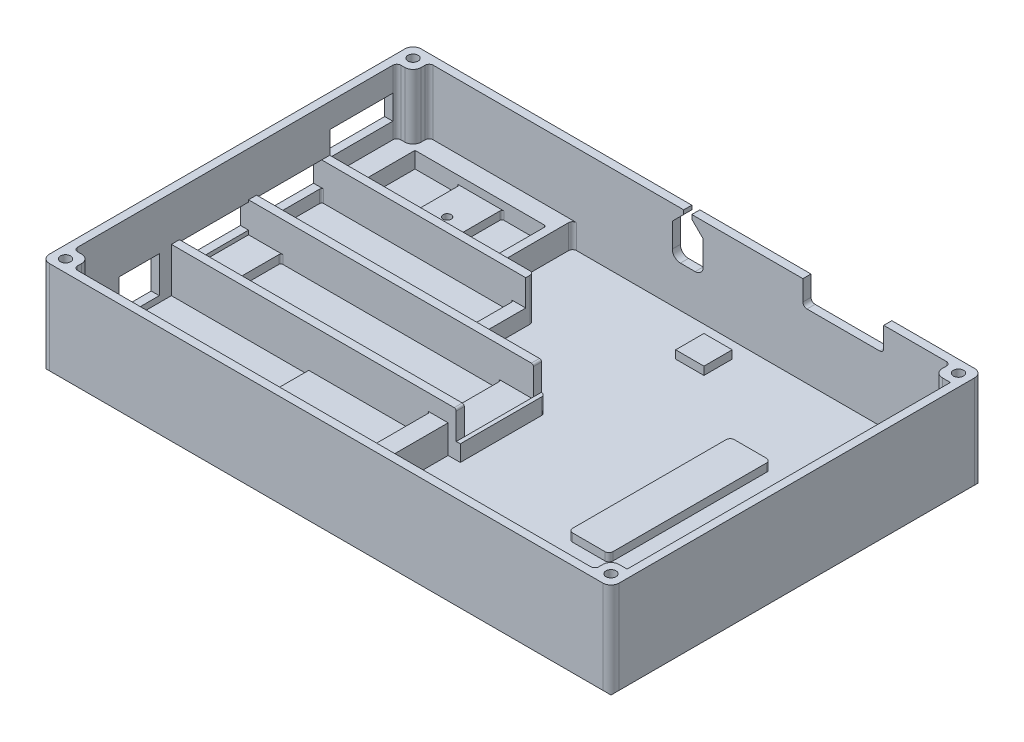
SolidWorks part; units mm, degrees
ref_plane "Front Plane" through (0, 0, 0) normal (0, 0, 1) x (1, 0, 0)
ref_plane "Top Plane" through (0, 0, 0) normal (0, 1, 0) x (1, 0, 0)
ref_plane "Right Plane" through (0, 0, 0) normal (1, 0, 0) x (0, 0, -1)
sketch "Sketch1" plane through (0, 0, 0) normal (0, 1, 0) x (1, 0, 0)
  line L1 (0, 0) -> (141, 0)
  line L2 (0, 0) -> (0, 92)
  line L3 (0, 92) -> (141, 92)
  line L4 (141, 0) -> (141, 92)
extrude "Base" add sketch "Sketch1" along normal blind 24
shell "Base Shell" thickness 2 removed face at (70.5, 24, -46)
chamfer "Chamfer1" distance 1 angle 45 4 edges at (0, 0, -46) (70.5, 0, -92) (141, 0, -46) (70.5, 0, 0)
sketch "Sketch2" plane through (0, 2, 0) normal (0, 1, 0) x (1, 0, 0)
  line L1 (0, 92) -> (6, 92)
  line L2 (0, 92) -> (0, 86)
  line L3 (0, 86) -> (6, 86)
  line L4 (6, 92) -> (6, 86)
  line L7 (141, 6) -> (135, 6)
  line L8 (0, 0) -> (6, 0)
  line L9 (0, 0) -> (0, 6)
  line L10 (0, 6) -> (6, 6)
  line L11 (6, 0) -> (6, 6)
  line L12 (135, 0) -> (135, 6)
  line L13 (141, 0) -> (135, 0)
  line L14 (141, 0) -> (141, 6)
  line L15 (141, 86) -> (135, 86)
  line L16 (135, 92) -> (135, 86)
  line L17 (141, 92) -> (135, 92)
  line L18 (141, 92) -> (141, 86)
extrude "Screw Support" add sketch "Sketch2" along normal blind 22
fillet "Base Corner Fillet" radius 2 4 edges at (141, 12.5, 0) (0, 12.5, 0) (0, 12.5, -92) (141, 12.5, -92)
fillet "Inner screw fillet" radius 2 4 edges at (135, 13, -86) (6, 13, -86) (6, 13, -6) (135, 13, -6)
sketch "Sketch5" plane through (0, 24, 0) normal (0, 1, 0) x (1, 0, 0)
  circle A0 centre (3, 89) radius 1.26
  circle A1 centre (3, 3) radius 1.26
  circle A2 centre (138, 3) radius 1.26
  circle A3 centre (138, 89) radius 1.26
extrude "Screw hole cut" cut sketch "Sketch5" against normal blind 15
sketch "Sketch7" plane through (0, 2, 0) normal (0, 1, 0) x (1, 0, 0)
  line L1 (2, 90) -> (41.5, 90)
  line L2 (2, 90) -> (2, 67.4)
  line L3 (2, 67.4) -> (41.5, 67.4)
  line L4 (41.5, 90) -> (41.5, 67.4)
extrude "Temp base extrude" add sketch "Sketch7" along normal blind 6
sketch "Sketch8" plane through (0, 8, 0) normal (0, 1, 0) x (1, 0, 0)
  line L15 (7, 85.5) -> (39.5, 85.5)
  line L16 (7, 85.5) -> (7, 69.4)
  line L17 (7, 69.4) -> (39.5, 69.4)
  line L18 (39.5, 85.5) -> (39.5, 69.4)
extrude "Temp base cut" cut sketch "Sketch8" against normal blind 2
sketch "Sketch9" plane through (0, 6, 0) normal (0, 1, 0) x (1, 0, 0)
  line L10 (7, 69.4) -> (39.5, 69.4) construction
  line L11 (7, 85.5) -> (18, 85.5)
  line L12 (7, 85.5) -> (7, 69.4)
  line L13 (7, 69.4) -> (18, 69.4)
  line L14 (18, 85.5) -> (18, 69.4)
  line L16 (39.5, 85.5) -> (28.5, 85.5)
  line L17 (39.5, 85.5) -> (39.5, 69.4)
  line L18 (39.5, 69.4) -> (28.5, 69.4)
  line L19 (28.5, 85.5) -> (28.5, 69.4)
extrude "Temp pins cut" cut sketch "Sketch9" against normal blind 2
sketch "Sketch10" plane through (0, 6, 0) normal (0, 1, 0) x (1, 0, 0)
  circle A0 centre (23.25, 77.2) radius 1
extrude "Temp screw hole cut" cut sketch "Sketch10" against normal blind 3
sketch "Sketch11" plane through (2, 0, 0) normal (1, 0, 0) x (0, 0, -1)
  line L4 (69.4, 12) -> (85, 12)
  line L5 (69.4, 12) -> (69.4, 18)
  line L6 (69.4, 18) -> (85, 18)
  line L7 (85, 12) -> (85, 18)
extrude "Temp output cut" cut sketch "Sketch11" against normal blind 3
sketch "Sketch13" plane through (0, 2, 0) normal (0, 1, 0) x (1, 0, 0)
  line L1 (2, 69.4) -> (52.5, 69.4)
  line L2 (2, 69.4) -> (2, 51.3)
  line L3 (2, 51.3) -> (52.5, 51.3)
  line L4 (52.5, 69.4) -> (52.5, 51.3)
extrude "Dimmer Base" add sketch "Sketch13" along normal blind 10.5
sketch "Sketch14" plane through (0, 12.5, 0) normal (0, 1, 0) x (1, 0, 0)
  line L0 (52.5, 51.3) -> (52.5, 69.4) construction
  line L1 (2, 51.3) -> (52.5, 51.3)
  line L2 (2, 51.3) -> (2, 67.4)
  line L3 (2, 67.4) -> (52.5, 67.4)
  line L4 (52.5, 51.3) -> (52.5, 67.4)
extrude "Dimmer Base Cut" cut sketch "Sketch14" against normal blind 9.1
sketch "Sketch16" plane through (0, 2, 0) normal (0, 1, 0) x (1, 0, 0)
  line L1 (52.5, 69.4) -> (49.5, 69.4)
  line L2 (52.5, 69.4) -> (52.5, 51.3)
  line L3 (52.5, 51.3) -> (49.5, 51.3)
  line L4 (49.5, 69.4) -> (49.5, 51.3)
extrude "Boss-Extrude5" add sketch "Sketch16" along normal blind 4
sketch "Sketch17" plane through (2, 0, 0) normal (1, 0, 0) x (0, 0, -1)
  line L1 (67.4, 3.4) -> (67.4, 12.5) construction
  line L2 (51.3, 6.5) -> (67.4, 6.5)
  line L3 (51.3, 6.5) -> (51.3, 12.5)
  line L4 (51.3, 12.5) -> (67.4, 12.5)
  line L5 (67.4, 6.5) -> (67.4, 12.5)
extrude "Cut-Extrude9" cut sketch "Sketch17" against normal blind 5
sketch "Sketch19" plane through (0, 2, 0) normal (0, 1, 0) x (1, 0, 0)
  line L1 (2, 51.3) -> (72.5, 51.3)
  line L2 (2, 51.3) -> (2, 30.2)
  line L3 (2, 30.2) -> (72.5, 30.2)
  line L4 (72.5, 51.3) -> (72.5, 30.2)
extrude "Relay Base" add sketch "Sketch19" along normal blind 11
sketch "Sketch20" plane through (0, 13, 0) normal (0, 1, 0) x (1, 0, 0)
  line L4 (2, 86) -> (2, 6) construction
  line L11 (2, 49.3) -> (72.5, 49.3)
  line L12 (2, 49.3) -> (2, 32.2)
  line L13 (2, 32.2) -> (72.5, 32.2)
  line L14 (72.5, 49.3) -> (72.5, 32.2)
  line L15 (72.5, 30.2) -> (72.5, 51.3) construction
extrude "Relay Base Cut" cut sketch "Sketch20" against normal blind 7.5
sketch "Sketch24" plane through (0, 5.5, 0) normal (0, 1, 0) x (1, 0, 0)
  line L1 (72.5, 49.3) -> (2, 49.3) construction
  line L3 (2, 32.2) -> (72.5, 32.2) construction
  line L4 (10, 49.3) -> (64.5, 49.3)
  line L5 (10, 49.3) -> (10, 32.2)
  line L6 (10, 32.2) -> (64.5, 32.2)
  line L7 (64.5, 49.3) -> (64.5, 32.2)
extrude "Relay Pins Cut" cut sketch "Sketch24" against normal blind 2.1
sketch "Sketch23" plane through (0, 2, 0) normal (0, 1, 0) x (1, 0, 0)
  line L1 (72.5, 51.3) -> (73.5, 51.3)
  line L2 (72.5, 51.3) -> (72.5, 30.2)
  line L3 (72.5, 30.2) -> (73.5, 30.2)
  line L4 (73.5, 51.3) -> (73.5, 30.2)
extrude "Relay Support Cut" add sketch "Sketch23" along normal blind 4
sketch "Sketch30" plane through (2, 0, 0) normal (1, 0, 0) x (0, 0, -1)
  line L0 (49.3, 5.5) -> (49.3, 13) construction
  line L1 (49.3, 6.5) -> (32.2, 6.5)
  line L2 (49.3, 6.5) -> (49.3, 12.5)
  line L3 (49.3, 12.5) -> (32.2, 12.5)
  line L4 (32.2, 6.5) -> (32.2, 12.5)
  line L5 (32.2, 5.5) -> (32.2, 13) construction
extrude "Relay Output Cut" cut sketch "Sketch30" against normal blind 16
sketch "Sketch22" plane through (0, 2, 0) normal (0, 1, 0) x (1, 0, 0)
  line L0 (78, 86) -> (85, 86)
  line L5 (85, 86) -> (85, 79)
  line L6 (85, 79) -> (78, 79)
  line L9 (78, 86) -> (78, 79)
  line L10 (78, 8) -> (85, 8)
  line L11 (85, 8) -> (85, 15)
  line L12 (85, 15) -> (78, 15)
  line L13 (78, 8) -> (78, 15)
  line L14 (139, 8) -> (139, 15)
  line L15 (132, 15) -> (139, 15)
  line L16 (132, 8) -> (132, 15)
  line L17 (139, 8) -> (132, 8)
  line L18 (139, 86) -> (132, 86)
  line L19 (132, 86) -> (132, 79)
  line L20 (132, 79) -> (139, 79)
  line L21 (139, 86) -> (139, 79)
extrude "Boss-Extrude13" add sketch "Sketch22" along normal blind 2
sketch "Sketch32" plane through (0, 2, 0) normal (0, 1, 0) x (1, 0, 0)
  line L3 (103.5, 27) -> (103.5, 67)
  line L6 (103.5, 67) -> (113.5, 67)
  line L7 (113.5, 27) -> (113.5, 67)
  line L11 (103.5, 27) -> (113.5, 27)
extrude "Support for esp32" add sketch "Sketch32" along normal blind 2
sketch "Sketch34" plane through (0, 2, 0) normal (0, 1, 0) x (1, 0, 0)
  line L1 (70.5, 30.2) -> (36, 30.2)
  line L3 (70.5, 30.2) -> (70.5, 13.2)
  line L12 (70.5, 13.2) -> (36, 13.2)
  line L13 (36, 30.2) -> (36, 13.2)
extrude "PSU part base" add sketch "Sketch34" along normal blind 7
sketch "Sketch35" plane through (0, 9, 0) normal (0, 1, 0) x (1, 0, 0)
  line L6 (36, 30.2) -> (66, 30.2)
  line L7 (36, 30.2) -> (36, 15.2)
  line L8 (36, 15.2) -> (66, 15.2)
  line L9 (66, 30.2) -> (66, 15.2)
extrude "PSU part cut" cut sketch "Sketch35" against normal blind 6
sketch "Sketch40" plane through (0, 0, 0) normal (-1, 0, 0) x (0, 0, 1)
  line L3 (-27.2, 12.5) -> (-17.2, 12.5)
  line L4 (-27.2, 12.5) -> (-27.2, 3.5)
  line L5 (-27.2, 3.5) -> (-17.2, 3.5)
  line L6 (-17.2, 12.5) -> (-17.2, 3.5)
extrude "PSU Cut" cut sketch "Sketch40" against normal blind 10
sketch "Sketch41" plane through (0, 0, -2) normal (0, 0, -1) x (-1, 0, 0)
  line L1 (-53, 1) -> (-27.5, 1)
  line L2 (-41, 17.5) -> (-27.5, 17.5)
  line L6 (-2, 1) -> (-139, 1) construction
  line L7 (-41, 17.5) -> (-53, 17.5)
  line L10 (-53, 17.5) -> (-53, 1)
  line L11 (-139, 1) -> (-2, 1) construction
  line L12 (-27.5, 1) -> (-27.5, 17.5)
extrude "Boss-Extrude14" add sketch "Sketch41" along normal blind 4
sketch "Sketch42" plane through (0, 17.5, 0) normal (0, 1, 0) x (1, 0, 0)
  line L1 (27.5, 6) -> (53, 6) construction
  line L3 (53, 6) -> (27.5, 6) construction
  line L4 (27.5, 2) -> (53, 2) construction
  line L5 (29.5, 6) -> (51, 6)
  line L6 (29.5, 6) -> (29.5, 2)
  line L7 (29.5, 2) -> (51, 2)
  line L8 (51, 6) -> (51, 2)
extrude "Cut-Extrude20" cut sketch "Sketch42" against normal blind 15.5
sketch "Sketch43" plane through (0, 2, 0) normal (0, 1, 0) x (1, 0, 0)
  line L0 (38.7896, 9.8552) -> (48.7896, 9.8552)
  line L1 (38.7896, 9.8552) -> (38.7896, 7.8552)
  line L9 (48.7896, 9.8552) -> (48.7896, 7.8552)
  line L10 (48.7896, 7.8552) -> (38.7896, 7.8552)
extrude "Boss-Extrude18" add sketch "Sketch43" along normal blind 10 contours L0 L9 L10 L1
fillet "0.5 mm fillet" radius 0.5 20 edges at (36, 9, -14.2) (72.5, 13, -50.3) (72.5, 13, -31.2) (66, 6, -15.2) (66, 6, -30.2) (64.5, 4.45, -32.2) (64.5, 4.45, -49.3) (10, 4.45, -32.2) (10, 4.45, -49.3) (49.5, 4.7, -51.3) (49.5, 4.7, -67.4) (2, 4.95, -51.3) (2, 4.95, -67.4) (18, 5, -69.4) (18, 5, -85.5) (28.5, 5, -85.5) (28.5, 5, -69.4) (39.5, 6, -69.4) (39.5, 6, -85.5) (7, 6, -69.4)
sketch "Sketch49" plane through (0, 0, -92) normal (0, 0, -1) x (-1, 0, 0)
  line L1 (-139, 24) -> (-2, 24) construction
  line L3 (-69, 24) -> (-71, 24)
  line L4 (-71, 24) -> (-71, 23)
  line L5 (-71, 23) -> (-73.8284, 20.1716)
  line L6 (-73.8284, 20.1716) -> (-73.8284, 12.1716)
  line L7 (-73.8284, 12.1716) -> (-66.1716, 12.1716)
  line L8 (-66.1716, 20.1716) -> (-66.1716, 12.1716)
  line L9 (-69, 23) -> (-66.1716, 20.1716)
  line L10 (-69, 24) -> (-69, 23)
  point P12 (-70, 12.1716)
extrude "Cut-Extrude23" cut sketch "Sketch49" against normal blind 10
fillet "Fillet3" radius 2 2 edges at (73.8284, 12.1716, -91) (66.1716, 12.1716, -91)
sketch "Sketch50" plane through (0, 24, 0) normal (0, 1, 0) x (1, 0, 0)
  line L1 (98.5, 90) -> (118.5, 90)
  line L2 (98.5, 90) -> (98.5, 92)
  line L3 (98.5, 92) -> (118.5, 92)
  line L4 (118.5, 90) -> (118.5, 92)
extrude "Cut-Extrude24" cut sketch "Sketch50" against normal blind 6 contours L3 L4 L1 L2
fillet "1 mm fillet" radius 1 18 edges at (41.5, 5, -90) (41.5, 5, -69.4) (52.5, 4, -51.3) (70.5, 5.5, -13.2) (73.5, 4, -51.3) (52.5, 7.25, -69.4) (103.5, 3, -67) (113.5, 3, -67) (103.5, 3, -27) (113.5, 3, -27) (135, 13, -2) (2, 13, -6) (6, 13, -2) (2, 16, -86) (6, 16, -90) (118.5, 18, -91) (98.5, 18, -91) (135, 13, -90)
sketch "Sketch51" plane through (0, 0, -92) normal (0, 0, -1) x (-1, 0, 0)
  line L0 (-6.5128, 16.5) -> (-5.8124, 16.5)
  line L1 (-5.5551, 14.6154) -> (-4.2692, 13)
  line L2 (-4.2692, 13) -> (-4.6577, 13)
  line L3 (-4.6577, 13) -> (-5.9435, 14.6154)
  line L4 (-5.9435, 14.6154) -> (-6.1987, 14.6154)
  line L5 (-6.1987, 14.6154) -> (-6.1987, 13)
  line L6 (-6.1987, 13) -> (-6.5128, 13)
  line L7 (-6.5128, 13) -> (-6.5128, 16.5)
  line L8 (-6.1987, 16.141) -> (-6.1987, 14.9744)
  line L9 (-6.1987, 14.9744) -> (-5.5579, 14.9695)
  line L10 (-5.5425, 16.141) -> (-6.1987, 16.141)
  line L11 (-13.109, 16.141) -> (-13.109, 16.5)
  line L12 (-13.109, 16.5) -> (-11.2692, 16.5)
  line L13 (-11.2692, 16.5) -> (-11.2692, 16.141)
  line L14 (-11.2692, 16.141) -> (-12.0321, 16.141)
  line L15 (-12.0321, 16.141) -> (-12.0321, 13)
  line L16 (-12.0321, 13) -> (-12.3462, 13)
  line L17 (-12.3462, 13) -> (-12.3462, 16.141)
  line L18 (-12.3462, 16.141) -> (-13.109, 16.141)
  line L19 (-14.9487, 16.5) -> (-13.3333, 13)
  line L20 (-13.3333, 13) -> (-13.6748, 13)
  line L21 (-13.6748, 13) -> (-14.1922, 14.1218)
  line L22 (-14.1922, 14.1218) -> (-15.7788, 14.1218)
  line L23 (-15.7788, 14.1218) -> (-16.3103, 13)
  line L24 (-16.3103, 13) -> (-16.6538, 13)
  line L25 (-16.6538, 13) -> (-14.9936, 16.5)
  line L26 (-14.9936, 16.5) -> (-14.9487, 16.5)
  line L27 (-14.9747, 15.8171) -> (-15.6078, 14.4808)
  line L28 (-15.6078, 14.4808) -> (-14.3577, 14.4808)
  line L29 (-14.3577, 14.4808) -> (-14.9747, 15.8171)
  line L30 (-19.9744, 13) -> (-19.9744, 16.5)
  line L31 (-19.9744, 16.5) -> (-19.9085, 16.5)
  line L32 (-19.9085, 16.5) -> (-17.5962, 13.7453)
  line L33 (-17.5962, 13.7453) -> (-17.5962, 16.5)
  line L34 (-17.5962, 16.5) -> (-17.2821, 16.5)
  line L35 (-17.2821, 16.5) -> (-17.2821, 13)
  line L36 (-17.2821, 13) -> (-17.3536, 13)
  line L37 (-17.3536, 13) -> (-19.6603, 15.7484)
  line L38 (-19.6603, 15.7484) -> (-19.6603, 13)
  line L39 (-19.6603, 13) -> (-19.9744, 13)
  line L40 (-21.1859, 16.5) -> (-20.8718, 16.5)
  line L41 (-20.8718, 16.5) -> (-20.8718, 13)
  line L42 (-20.8718, 13) -> (-21.1859, 13)
  line L43 (-21.1859, 13) -> (-21.1859, 16.5)
  line L44 (-22.1282, 15.9026) -> (-22.3974, 15.6474)
  line L45 (-22.2179, 14.3462) -> (-23.3846, 14.3462)
  line L46 (-23.3846, 14.3462) -> (-23.3846, 14.7051)
  line L47 (-23.3846, 14.7051) -> (-21.9038, 14.7051)
  line L48 (-26.3462, 15.9026) -> (-26.6154, 15.6474)
  line L49 (-26.4359, 14.3462) -> (-27.6026, 14.3462)
  line L50 (-27.6026, 14.3462) -> (-27.6026, 14.7051)
  line L51 (-27.6026, 14.7051) -> (-26.1218, 14.7051)
  line L52 (-31.8654, 16.5) -> (-30.25, 13)
  line L53 (-30.25, 13) -> (-30.5914, 13)
  line L54 (-30.5914, 13) -> (-31.1089, 14.1218)
  line L55 (-31.1089, 14.1218) -> (-32.6955, 14.1218)
  line L56 (-32.6955, 14.1218) -> (-33.227, 13)
  line L57 (-33.227, 13) -> (-33.5705, 13)
  line L58 (-33.5705, 13) -> (-31.9103, 16.5)
  line L59 (-31.9103, 16.5) -> (-31.8654, 16.5)
  line L60 (-31.8913, 15.8171) -> (-32.5244, 14.4808)
  line L61 (-32.5244, 14.4808) -> (-31.2743, 14.4808)
  line L62 (-31.2743, 14.4808) -> (-31.8913, 15.8171)
  line L63 (-34.2436, 15.9026) -> (-34.5128, 15.6474)
  line L64 (-34.3333, 14.3462) -> (-35.5, 14.3462)
  line L65 (-35.5, 14.3462) -> (-35.5, 14.7051)
  line L66 (-35.5, 14.7051) -> (-34.0192, 14.7051)
  spline S0 degree 3 poles (-5.8124, 16.5) (-5.7227, 16.4995) (-5.594, 16.4998) (-5.4305, 16.4931) (-5.3255, 16.489) (-5.2323, 16.4815) (-5.1311, 16.4727) (-5.0615, 16.4617) (-5.0194, 16.4523) knots 0 0 0 0 0.338434 0.484822 0.617158 0.734698 0.837385 1 1 1 1
  spline S1 degree 3 poles (-5.0194, 16.4523) (-4.9685, 16.4411) (-4.8943, 16.4178) (-4.8007, 16.3764) (-4.7349, 16.3404) (-4.6732, 16.2989) (-4.6148, 16.2524) (-4.5597, 16.2013) (-4.5099, 16.1443) (-4.463, 16.0844) (-4.4234, 16.0197) (-4.3892, 15.952) (-4.3621, 15.8807) (-4.3402, 15.8065) (-4.3192, 15.701) (-4.314, 15.6193) (-4.3141, 15.564) knots 0 0 0 0 0.127064 0.188745 0.249132 0.309453 0.369827 0.43065 0.492352 0.554072 0.61569 0.676798 0.738439 0.801317 0.865185 1 1 1 1
  spline S2 degree 3 poles (-4.3141, 15.564) (-4.3138, 15.4732) (-4.3293, 15.3384) (-4.389, 15.1711) (-4.4493, 15.057) (-4.5261, 14.954) (-4.6184, 14.8637) (-4.7263, 14.788) (-4.8267, 14.7356) (-4.9154, 14.702) (-4.9885, 14.6783) (-5.0681, 14.6601) (-5.1537, 14.6437) (-5.2454, 14.6314) (-5.3798, 14.6189) (-5.4838, 14.6156) (-5.5551, 14.6154) knots 0 0 0 0 0.153721 0.226714 0.299191 0.37119 0.443006 0.516689 0.593217 0.633873 0.676989 0.7229 0.771959 0.824211 0.879379 1 1 1 1
  spline S3 degree 3 poles (-5.5579, 14.9695) (-5.4999, 14.9685) (-5.4159, 14.9716) (-5.308, 14.978) (-5.2359, 14.9849) (-5.1699, 14.9939) (-5.11, 15.0051) (-5.0561, 15.0181) (-4.9932, 15.0383) (-4.9229, 15.0703) (-4.8466, 15.1169) (-4.7816, 15.1755) (-4.7267, 15.2424) (-4.6826, 15.3161) (-4.6407, 15.4224) (-4.628, 15.5075) (-4.6282, 15.5647) knots 0 0 0 0 0.138913 0.201185 0.259124 0.312255 0.360682 0.405086 0.445102 0.518778 0.589462 0.658462 0.727283 0.796322 0.863175 1 1 1 1
  spline S4 degree 3 poles (-4.6282, 15.5647) (-4.6284, 15.6203) (-4.64, 15.7043) (-4.6842, 15.8074) (-4.7284, 15.8795) (-4.7825, 15.945) (-4.8458, 16.0011) (-4.9167, 16.0473) (-4.9829, 16.0769) (-5.0422, 16.095) (-5.0936, 16.1077) (-5.1517, 16.118) (-5.2168, 16.1262) (-5.2886, 16.1332) (-5.3979, 16.1399) (-5.4833, 16.1412) (-5.5425, 16.141) knots 0 0 0 0 0.136365 0.204019 0.273064 0.342913 0.410965 0.479169 0.549308 0.587652 0.630647 0.678879 0.731934 0.791111 0.855283 1 1 1 1
  spline S5 degree 3 poles (-9.0929, 16.5897) (-8.9658, 16.589) (-8.7769, 16.5755) (-8.5352, 16.5175) (-8.3636, 16.4607) (-8.2011, 16.3848) (-8.0465, 16.2931) (-7.9001, 16.1846) (-7.7638, 16.0602) (-7.6392, 15.9248) (-7.5294, 15.7803) (-7.4373, 15.6276) (-7.3617, 15.4672) (-7.3025, 15.2993) (-7.2469, 15.0613) (-7.2305, 14.8764) (-7.2308, 14.7514) knots 0 0 0 0 0.130749 0.193413 0.254989 0.316114 0.377262 0.439401 0.502971 0.566525 0.628231 0.689091 0.749345 0.81017 0.87161 1 1 1 1
  spline S6 degree 3 poles (-7.2308, 14.7514) (-7.2305, 14.6273) (-7.2469, 14.4436) (-7.3026, 14.2071) (-7.3612, 14.0394) (-7.4364, 13.8788) (-7.5291, 13.7258) (-7.6382, 13.5804) (-7.7624, 13.444) (-7.8978, 13.319) (-8.043, 13.2101) (-8.1948, 13.1164) (-8.3551, 13.0416) (-8.5218, 12.9819) (-8.7578, 12.9265) (-8.941, 12.9099) (-9.0649, 12.9103) knots 0 0 0 0 0.128569 0.19032 0.251378 0.312388 0.373789 0.436431 0.500567 0.564687 0.627136 0.688455 0.749246 0.810155 0.871671 1 1 1 1
  spline S7 degree 3 poles (-9.0649, 12.9103) (-9.1899, 12.91) (-9.3751, 12.9264) (-9.6132, 12.982) (-9.7817, 13.0405) (-9.9425, 13.1161) (-10.096, 13.2083) (-10.2415, 13.3177) (-10.3779, 13.4419) (-10.5026, 13.5771) (-10.6114, 13.7219) (-10.7036, 13.8735) (-10.779, 14.0324) (-10.8386, 14.1978) (-10.8939, 14.4312) (-10.9106, 14.6123) (-10.9103, 14.7346) knots 0 0 0 0 0.129747 0.192072 0.253459 0.31457 0.37628 0.439026 0.503267 0.567493 0.629705 0.691 0.751452 0.812004 0.87315 1 1 1 1
  spline S8 degree 3 poles (-10.9103, 14.7346) (-10.9112, 14.8174) (-10.9024, 14.9407) (-10.8773, 15.1027) (-10.8507, 15.2213) (-10.8159, 15.3372) (-10.7749, 15.4514) (-10.7247, 15.5626) (-10.668, 15.6713) (-10.6048, 15.7759) (-10.5349, 15.8748) (-10.4609, 15.9688) (-10.3797, 16.0554) (-10.2941, 16.1373) (-10.2026, 16.213) (-10.1059, 16.2834) (-10.0034, 16.3468) (-9.8978, 16.4042) (-9.7889, 16.4534) (-9.6783, 16.4956) (-9.5653, 16.5299) (-9.4504, 16.5569) (-9.2932, 16.5818) (-9.1734, 16.5907) (-9.0929, 16.5897) knots 0 0 0 0 0.085873 0.12812 0.170152 0.211918 0.253753 0.296006 0.338443 0.381015 0.42282 0.464089 0.505126 0.545975 0.586985 0.628339 0.670084 0.711992 0.753039 0.794049 0.834886 0.875498 0.916547 1 1 1 1
  spline S9 degree 3 poles (-9.0775, 16.2308) (-9.1437, 16.2317) (-9.2423, 16.2242) (-9.3721, 16.2038) (-9.4678, 16.1822) (-9.5619, 16.1528) (-9.6551, 16.119) (-9.7467, 16.0778) (-9.8364, 16.0312) (-9.9233, 15.9796) (-10.0053, 15.9227) (-10.0826, 15.8616) (-10.1551, 15.7963) (-10.2224, 15.7265) (-10.286, 15.6531) (-10.3433, 15.5742) (-10.3958, 15.4918) (-10.4428, 15.406) (-10.4845, 15.3178) (-10.5187, 15.2264) (-10.5466, 15.1329) (-10.5696, 15.0373) (-10.5895, 14.9049) (-10.5972, 14.804) (-10.5962, 14.736) knots 0 0 0 0 0.083645 0.124984 0.166247 0.207702 0.249631 0.291742 0.334743 0.37746 0.419556 0.461044 0.502096 0.542891 0.583801 0.624864 0.666225 0.707399 0.748557 0.789655 0.83074 0.87207 0.913993 1 1 1 1
  spline S10 degree 3 poles (-10.5962, 14.736) (-10.5965, 14.6365) (-10.5825, 14.4894) (-10.5365, 14.3001) (-10.4867, 14.1664) (-10.4244, 14.0381) (-10.3474, 13.9162) (-10.2561, 13.8007) (-10.1524, 13.6924) (-10.0391, 13.5935) (-9.9188, 13.5068) (-9.7927, 13.4334) (-9.6606, 13.3736) (-9.5232, 13.3262) (-9.3292, 13.2821) (-9.1791, 13.2683) (-9.0775, 13.2692) knots 0 0 0 0 0.126899 0.187747 0.24815 0.308586 0.369583 0.431827 0.49618 0.560668 0.623504 0.68526 0.746537 0.808327 0.870486 1 1 1 1
  spline S11 degree 3 poles (-9.0775, 13.2692) (-9.0089, 13.2689) (-8.9064, 13.2748) (-8.7719, 13.2954) (-8.6736, 13.3173) (-8.5775, 13.3448) (-8.483, 13.3774) (-8.3912, 13.418) (-8.3009, 13.463) (-8.2145, 13.5142) (-8.132, 13.5693) (-8.0556, 13.6302) (-7.9832, 13.6946) (-7.9155, 13.7635) (-7.8531, 13.837) (-7.7962, 13.9156) (-7.7437, 13.9979) (-7.6969, 14.0839) (-7.6561, 14.1724) (-7.6215, 14.2632) (-7.5936, 14.3565) (-7.5717, 14.4521) (-7.5513, 14.5838) (-7.544, 14.6843) (-7.5449, 14.7521) knots 0 0 0 0 0.086538 0.129177 0.171436 0.213416 0.255266 0.297369 0.339941 0.382347 0.423953 0.464871 0.505572 0.546003 0.586568 0.627065 0.668271 0.709549 0.750428 0.791096 0.832027 0.873136 0.914611 1 1 1 1
  spline S12 degree 3 poles (-7.5449, 14.7521) (-7.544, 14.8194) (-7.5513, 14.9192) (-7.5717, 15.05) (-7.5935, 15.1447) (-7.6215, 15.2368) (-7.6561, 15.3262) (-7.6969, 15.4133) (-7.7437, 15.4979) (-7.7963, 15.5791) (-7.8538, 15.6567) (-7.9172, 15.7293) (-7.9846, 15.7986) (-8.0578, 15.8632) (-8.1364, 15.9232) (-8.2194, 15.9798) (-8.3073, 16.031) (-8.3981, 16.0782) (-8.4912, 16.1186) (-8.5856, 16.153) (-8.6811, 16.1823) (-8.7785, 16.2037) (-8.9104, 16.2242) (-9.0104, 16.2317) (-9.0775, 16.2308) knots 0 0 0 0 0.08513 0.126473 0.167453 0.207976 0.248249 0.28875 0.32967 0.370537 0.411129 0.451819 0.492406 0.533486 0.575263 0.617441 0.660672 0.70394 0.746868 0.789079 0.831104 0.873238 0.915166 1 1 1 1
  spline S13 degree 3 poles (-22.3974, 15.6474) (-22.4915, 15.7402) (-22.6422, 15.8665) (-22.8632, 16.002) (-23.0329, 16.0839) (-23.2043, 16.1492) (-23.4286, 16.2107) (-23.5991, 16.2312) (-23.7113, 16.2308) knots 0 0 0 0 0.269043 0.398517 0.5271 0.652283 0.77168 1 1 1 1
  spline S14 degree 3 poles (-23.7113, 16.2308) (-23.7791, 16.2316) (-23.8801, 16.2242) (-24.0132, 16.2038) (-24.1115, 16.1819) (-24.2088, 16.1541) (-24.3047, 16.1193) (-24.3993, 16.0787) (-24.4919, 16.0319) (-24.5816, 15.9804) (-24.6664, 15.9233) (-24.7467, 15.8625) (-24.8211, 15.7965) (-24.8899, 15.7258) (-24.9548, 15.6517) (-25.0136, 15.5723) (-25.0667, 15.4889) (-25.1141, 15.4031) (-25.1559, 15.3157) (-25.191, 15.227) (-25.2188, 15.1368) (-25.2417, 15.0459) (-25.2633, 14.9224) (-25.2684, 14.8282) (-25.2692, 14.7654) knots 0 0 0 0 0.085571 0.127719 0.170068 0.212787 0.255482 0.298877 0.342861 0.386528 0.429532 0.471886 0.513729 0.555082 0.596535 0.63812 0.679822 0.721331 0.761888 0.802199 0.841806 0.88106 0.920633 1 1 1 1
  spline S15 degree 3 poles (-25.2692, 14.7654) (-25.2685, 14.701) (-25.2634, 14.6043) (-25.2394, 14.4777) (-25.2154, 14.3841) (-25.1854, 14.2914) (-25.1481, 14.2001) (-25.1038, 14.1101) (-25.0526, 14.0223) (-24.9964, 13.9368) (-24.9334, 13.8562) (-24.8666, 13.7795) (-24.7934, 13.7085) (-24.7161, 13.6411) (-24.6326, 13.5793) (-24.5444, 13.5218) (-24.4514, 13.4694) (-24.3546, 13.4226) (-24.2553, 13.3809) (-24.1533, 13.3467) (-24.049, 13.3187) (-23.9427, 13.2959) (-23.7963, 13.2759) (-23.6852, 13.2682) (-23.6104, 13.2692) knots 0 0 0 0 0.077882 0.116652 0.155416 0.194618 0.234261 0.274547 0.315667 0.35702 0.398083 0.439098 0.479833 0.521274 0.562841 0.605292 0.648409 0.691727 0.735149 0.778369 0.821661 0.865524 0.909731 1 1 1 1
  spline S16 degree 3 poles (-23.6104, 13.2692) (-23.5213, 13.2693) (-23.3896, 13.2783) (-23.2191, 13.3092) (-23.0988, 13.3423) (-22.984, 13.3847) (-22.8741, 13.4357) (-22.77, 13.4973) (-22.6715, 13.5669) (-22.5807, 13.6444) (-22.4989, 13.728) (-22.4272, 13.8174) (-22.3647, 13.912) (-22.3131, 14.0125) (-22.2557, 14.1553) (-22.2295, 14.2689) (-22.2179, 14.3462) knots 0 0 0 0 0.138694 0.204918 0.269441 0.332636 0.395302 0.457764 0.520657 0.582852 0.643315 0.70258 0.760908 0.81949 0.878269 1 1 1 1
  spline S17 degree 3 poles (-21.9038, 14.7051) (-21.9047, 14.5743) (-21.9184, 14.3819) (-21.9702, 14.1359) (-22.0218, 13.966) (-22.0887, 13.8067) (-22.17, 13.6578) (-22.2672, 13.5204) (-22.3767, 13.3934) (-22.4996, 13.2801) (-22.6326, 13.1805) (-22.7758, 13.0966) (-22.9293, 13.0283) (-23.0923, 12.9751) (-23.3281, 12.9234) (-23.5125, 12.9108) (-23.6377, 12.9103) knots 0 0 0 0 0.139493 0.204635 0.267406 0.328446 0.388397 0.447734 0.507392 0.566768 0.625478 0.684067 0.743248 0.804033 0.866499 1 1 1 1
  spline S18 degree 3 poles (-23.6377, 12.9103) (-23.7157, 12.9104) (-23.831, 12.9155) (-23.9822, 12.9322) (-24.0909, 12.9507) (-24.1968, 12.9735) (-24.2995, 13.0026) (-24.3991, 13.0362) (-24.4961, 13.0745) (-24.5893, 13.1189) (-24.6794, 13.1682) (-24.7666, 13.2222) (-24.8506, 13.2818) (-24.9316, 13.3466) (-25.0359, 13.4406) (-25.1082, 13.5182) (-25.1542, 13.5721) knots 0 0 0 0 0.136557 0.202094 0.266464 0.329769 0.391879 0.453271 0.514115 0.57439 0.634142 0.693923 0.754152 0.81447 0.875661 1 1 1 1
  spline S19 degree 3 poles (-25.1542, 13.5721) (-25.2238, 13.6552) (-25.3181, 13.7865) (-25.4179, 13.9754) (-25.4783, 14.121) (-25.5254, 14.2717) (-25.5711, 14.481) (-25.5825, 14.6428) (-25.5833, 14.7514) knots 0 0 0 0 0.253668 0.376738 0.499344 0.621999 0.745699 1 1 1 1
  spline S20 degree 3 poles (-25.5833, 14.7514) (-25.5843, 14.8333) (-25.5754, 14.9552) (-25.5505, 15.1151) (-25.5235, 15.2322) (-25.4894, 15.3471) (-25.4468, 15.4598) (-25.3973, 15.5705) (-25.3397, 15.6784) (-25.2756, 15.782) (-25.2061, 15.8809) (-25.1301, 15.9734) (-25.0488, 16.0606) (-24.9614, 16.1414) (-24.8687, 16.2166) (-24.7705, 16.2862) (-24.6665, 16.3492) (-24.5584, 16.4057) (-24.4464, 16.4553) (-24.3304, 16.4963) (-24.2114, 16.5311) (-24.0885, 16.5568) (-23.9186, 16.5821) (-23.7885, 16.5907) (-23.7008, 16.5897) knots 0 0 0 0 0.083544 0.124643 0.165303 0.206171 0.246971 0.288329 0.329987 0.371797 0.412738 0.453459 0.494001 0.534381 0.574952 0.615892 0.65725 0.699007 0.740486 0.782325 0.824567 0.867041 0.9105 1 1 1 1
  spline S21 degree 3 poles (-23.7008, 16.5897) (-23.629, 16.5895) (-23.5218, 16.5844) (-23.3805, 16.5674) (-23.2768, 16.5502) (-23.1748, 16.5267) (-23.0745, 16.4987) (-22.9755, 16.466) (-22.8783, 16.427) (-22.7821, 16.3827) (-22.6865, 16.3329) (-22.5917, 16.2767) (-22.4977, 16.2139) (-22.4037, 16.1456) (-22.2787, 16.0432) (-22.1871, 15.9613) (-22.1282, 15.9026) knots 0 0 0 0 0.122179 0.182216 0.241864 0.30096 0.359969 0.419033 0.478069 0.537993 0.59896 0.661321 0.725248 0.79122 0.858746 1 1 1 1
  spline S22 degree 3 poles (-26.6154, 15.6474) (-26.7094, 15.7402) (-26.8601, 15.8665) (-27.0811, 16.002) (-27.2508, 16.0839) (-27.4223, 16.1492) (-27.6466, 16.2107) (-27.817, 16.2312) (-27.9293, 16.2308) knots 0 0 0 0 0.269043 0.398517 0.5271 0.652283 0.77168 1 1 1 1
  spline S23 degree 3 poles (-27.9293, 16.2308) (-27.9971, 16.2316) (-28.098, 16.2242) (-28.2311, 16.2038) (-28.3295, 16.1819) (-28.4267, 16.1541) (-28.5226, 16.1193) (-28.6173, 16.0787) (-28.7098, 16.0319) (-28.7996, 15.9804) (-28.8843, 15.9233) (-28.9647, 15.8625) (-29.039, 15.7965) (-29.1078, 15.7258) (-29.1728, 15.6517) (-29.2316, 15.5723) (-29.2847, 15.4889) (-29.332, 15.4031) (-29.3738, 15.3157) (-29.4089, 15.227) (-29.4367, 15.1368) (-29.4596, 15.0459) (-29.4812, 14.9224) (-29.4864, 14.8282) (-29.4872, 14.7654) knots 0 0 0 0 0.085571 0.127719 0.170068 0.212787 0.255482 0.298877 0.342861 0.386528 0.429532 0.471886 0.513729 0.555082 0.596535 0.63812 0.679822 0.721331 0.761888 0.802199 0.841806 0.88106 0.920633 1 1 1 1
  spline S24 degree 3 poles (-29.4872, 14.7654) (-29.4864, 14.701) (-29.4813, 14.6043) (-29.4573, 14.4777) (-29.4334, 14.3841) (-29.4034, 14.2914) (-29.366, 14.2001) (-29.3217, 14.1101) (-29.2705, 14.0223) (-29.2143, 13.9368) (-29.1514, 13.8562) (-29.0845, 13.7795) (-29.0113, 13.7085) (-28.9341, 13.6411) (-28.8505, 13.5793) (-28.7623, 13.5218) (-28.6693, 13.4694) (-28.5725, 13.4226) (-28.4733, 13.3809) (-28.3712, 13.3467) (-28.267, 13.3187) (-28.1606, 13.2959) (-28.0143, 13.2759) (-27.9031, 13.2682) (-27.8283, 13.2692) knots 0 0 0 0 0.077882 0.116652 0.155416 0.194618 0.234261 0.274547 0.315667 0.35702 0.398083 0.439098 0.479833 0.521274 0.562841 0.605292 0.648409 0.691727 0.735149 0.778369 0.821661 0.865524 0.909731 1 1 1 1
  spline S25 degree 3 poles (-27.8283, 13.2692) (-27.7392, 13.2693) (-27.6075, 13.2783) (-27.437, 13.3092) (-27.3168, 13.3423) (-27.2019, 13.3847) (-27.092, 13.4357) (-26.988, 13.4973) (-26.8894, 13.5669) (-26.7987, 13.6444) (-26.7168, 13.728) (-26.6452, 13.8174) (-26.5827, 13.912) (-26.531, 14.0125) (-26.4737, 14.1553) (-26.4475, 14.2689) (-26.4359, 14.3462) knots 0 0 0 0 0.138694 0.204918 0.269441 0.332636 0.395302 0.457764 0.520657 0.582852 0.643315 0.70258 0.760908 0.81949 0.878269 1 1 1 1
  spline S26 degree 3 poles (-26.1218, 14.7051) (-26.1226, 14.5743) (-26.1363, 14.3819) (-26.1881, 14.1359) (-26.2397, 13.966) (-26.3066, 13.8067) (-26.388, 13.6578) (-26.4852, 13.5204) (-26.5947, 13.3934) (-26.7176, 13.2801) (-26.8505, 13.1805) (-26.9938, 13.0966) (-27.1472, 13.0283) (-27.3103, 12.9751) (-27.5461, 12.9234) (-27.7304, 12.9108) (-27.8557, 12.9103) knots 0 0 0 0 0.139493 0.204635 0.267406 0.328446 0.388397 0.447734 0.507392 0.566768 0.625478 0.684067 0.743248 0.804033 0.866499 1 1 1 1
  spline S27 degree 3 poles (-27.8557, 12.9103) (-27.9336, 12.9104) (-28.0489, 12.9155) (-28.2001, 12.9322) (-28.3088, 12.9507) (-28.4148, 12.9735) (-28.5174, 13.0026) (-28.6171, 13.0362) (-28.714, 13.0745) (-28.8073, 13.1189) (-28.8973, 13.1682) (-28.9846, 13.2222) (-29.0685, 13.2818) (-29.1496, 13.3466) (-29.2538, 13.4406) (-29.3261, 13.5182) (-29.3722, 13.5721) knots 0 0 0 0 0.136557 0.202094 0.266464 0.329769 0.391879 0.453271 0.514115 0.57439 0.634142 0.693923 0.754152 0.81447 0.875661 1 1 1 1
  spline S28 degree 3 poles (-29.3722, 13.5721) (-29.4418, 13.6552) (-29.536, 13.7865) (-29.6358, 13.9754) (-29.6962, 14.121) (-29.7433, 14.2717) (-29.789, 14.481) (-29.8004, 14.6428) (-29.8013, 14.7514) knots 0 0 0 0 0.253668 0.376738 0.499344 0.621999 0.745699 1 1 1 1
  spline S29 degree 3 poles (-29.8013, 14.7514) (-29.8022, 14.8333) (-29.7933, 14.9552) (-29.7684, 15.1151) (-29.7414, 15.2322) (-29.7073, 15.3471) (-29.6648, 15.4598) (-29.6152, 15.5705) (-29.5576, 15.6784) (-29.4936, 15.782) (-29.424, 15.8809) (-29.348, 15.9734) (-29.2668, 16.0606) (-29.1794, 16.1414) (-29.0866, 16.2166) (-28.9884, 16.2862) (-28.8845, 16.3492) (-28.7764, 16.4057) (-28.6643, 16.4553) (-28.5484, 16.4963) (-28.4294, 16.5311) (-28.3064, 16.5568) (-28.1365, 16.5821) (-28.0064, 16.5907) (-27.9188, 16.5897) knots 0 0 0 0 0.083544 0.124643 0.165303 0.206171 0.246971 0.288329 0.329987 0.371797 0.412738 0.453459 0.494001 0.534381 0.574952 0.615892 0.65725 0.699007 0.740486 0.782325 0.824567 0.867041 0.9105 1 1 1 1
  spline S30 degree 3 poles (-27.9188, 16.5897) (-27.8469, 16.5895) (-27.7397, 16.5844) (-27.5985, 16.5674) (-27.4947, 16.5502) (-27.3928, 16.5267) (-27.2924, 16.4987) (-27.1935, 16.466) (-27.0962, 16.427) (-27.0001, 16.3827) (-26.9044, 16.3329) (-26.8097, 16.2767) (-26.7156, 16.2139) (-26.6217, 16.1456) (-26.4966, 16.0432) (-26.4051, 15.9613) (-26.3462, 15.9026) knots 0 0 0 0 0.122179 0.182216 0.241864 0.30096 0.359969 0.419033 0.478069 0.537993 0.59896 0.661321 0.725248 0.79122 0.858746 1 1 1 1
  spline S31 degree 3 poles (-34.5128, 15.6474) (-34.6068, 15.7402) (-34.7576, 15.8665) (-34.9786, 16.002) (-35.1482, 16.0839) (-35.3197, 16.1492) (-35.544, 16.2107) (-35.7145, 16.2312) (-35.8267, 16.2308) knots 0 0 0 0 0.269043 0.398517 0.5271 0.652283 0.77168 1 1 1 1
  spline S32 degree 3 poles (-35.8267, 16.2308) (-35.8945, 16.2316) (-35.9955, 16.2242) (-36.1286, 16.2038) (-36.2269, 16.1819) (-36.3242, 16.1541) (-36.42, 16.1193) (-36.5147, 16.0787) (-36.6073, 16.0319) (-36.697, 15.9804) (-36.7818, 15.9233) (-36.8621, 15.8625) (-36.9364, 15.7965) (-37.0053, 15.7258) (-37.0702, 15.6517) (-37.129, 15.5723) (-37.1821, 15.4889) (-37.2295, 15.4031) (-37.2713, 15.3157) (-37.3064, 15.227) (-37.3341, 15.1368) (-37.357, 15.0459) (-37.3787, 14.9224) (-37.3838, 14.8282) (-37.3846, 14.7654) knots 0 0 0 0 0.085571 0.127719 0.170068 0.212787 0.255482 0.298877 0.342861 0.386528 0.429532 0.471886 0.513729 0.555082 0.596535 0.63812 0.679822 0.721331 0.761888 0.802199 0.841806 0.88106 0.920633 1 1 1 1
  spline S33 degree 3 poles (-37.3846, 14.7654) (-37.3839, 14.701) (-37.3788, 14.6043) (-37.3547, 14.4777) (-37.3308, 14.3841) (-37.3008, 14.2914) (-37.2634, 14.2001) (-37.2192, 14.1101) (-37.1679, 14.0223) (-37.1118, 13.9368) (-37.0488, 13.8562) (-36.9819, 13.7795) (-36.9087, 13.7085) (-36.8315, 13.6411) (-36.748, 13.5793) (-36.6598, 13.5218) (-36.5668, 13.4694) (-36.47, 13.4226) (-36.3707, 13.3809) (-36.2687, 13.3467) (-36.1644, 13.3187) (-36.058, 13.2959) (-35.9117, 13.2759) (-35.8005, 13.2682) (-35.7258, 13.2692) knots 0 0 0 0 0.077882 0.116652 0.155416 0.194618 0.234261 0.274547 0.315667 0.35702 0.398083 0.439098 0.479833 0.521274 0.562841 0.605292 0.648409 0.691727 0.735149 0.778369 0.821661 0.865524 0.909731 1 1 1 1
  spline S34 degree 3 poles (-35.7258, 13.2692) (-35.6367, 13.2693) (-35.505, 13.2783) (-35.3345, 13.3092) (-35.2142, 13.3423) (-35.0994, 13.3847) (-34.9895, 13.4357) (-34.8854, 13.4973) (-34.7869, 13.5669) (-34.6961, 13.6444) (-34.6143, 13.728) (-34.5426, 13.8174) (-34.4801, 13.912) (-34.4284, 14.0125) (-34.3711, 14.1553) (-34.3449, 14.2689) (-34.3333, 14.3462) knots 0 0 0 0 0.138694 0.204918 0.269441 0.332636 0.395302 0.457764 0.520657 0.582852 0.643315 0.70258 0.760908 0.81949 0.878269 1 1 1 1
  spline S35 degree 3 poles (-34.0192, 14.7051) (-34.0201, 14.5743) (-34.0337, 14.3819) (-34.0855, 14.1359) (-34.1372, 13.966) (-34.204, 13.8067) (-34.2854, 13.6578) (-34.3826, 13.5204) (-34.4921, 13.3934) (-34.615, 13.2801) (-34.748, 13.1805) (-34.8912, 13.0966) (-35.0446, 13.0283) (-35.2077, 12.9751) (-35.4435, 12.9234) (-35.6279, 12.9108) (-35.7531, 12.9103) knots 0 0 0 0 0.139493 0.204635 0.267406 0.328446 0.388397 0.447734 0.507392 0.566768 0.625478 0.684067 0.743248 0.804033 0.866499 1 1 1 1
  spline S36 degree 3 poles (-35.7531, 12.9103) (-35.831, 12.9104) (-35.9463, 12.9155) (-36.0976, 12.9322) (-36.2063, 12.9507) (-36.3122, 12.9735) (-36.4148, 13.0026) (-36.5145, 13.0362) (-36.6114, 13.0745) (-36.7047, 13.1189) (-36.7947, 13.1682) (-36.882, 13.2222) (-36.966, 13.2818) (-37.047, 13.3466) (-37.1513, 13.4406) (-37.2236, 13.5182) (-37.2696, 13.5721) knots 0 0 0 0 0.136557 0.202094 0.266464 0.329769 0.391879 0.453271 0.514115 0.57439 0.634142 0.693923 0.754152 0.81447 0.875661 1 1 1 1
  spline S37 degree 3 poles (-37.2696, 13.5721) (-37.3392, 13.6552) (-37.4334, 13.7865) (-37.5333, 13.9754) (-37.5937, 14.121) (-37.6408, 14.2717) (-37.6865, 14.481) (-37.6978, 14.6428) (-37.6987, 14.7514) knots 0 0 0 0 0.253668 0.376738 0.499344 0.621999 0.745699 1 1 1 1
  spline S38 degree 3 poles (-37.6987, 14.7514) (-37.6997, 14.8333) (-37.6908, 14.9552) (-37.6659, 15.1151) (-37.6389, 15.2322) (-37.6048, 15.3471) (-37.5622, 15.4598) (-37.5127, 15.5705) (-37.4551, 15.6784) (-37.391, 15.782) (-37.3214, 15.8809) (-37.2454, 15.9734) (-37.1642, 16.0606) (-37.0768, 16.1414) (-36.9841, 16.2166) (-36.8859, 16.2862) (-36.7819, 16.3492) (-36.6738, 16.4057) (-36.5617, 16.4553) (-36.4458, 16.4963) (-36.3268, 16.5311) (-36.2039, 16.5568) (-36.034, 16.5821) (-35.9039, 16.5907) (-35.8162, 16.5897) knots 0 0 0 0 0.083544 0.124643 0.165303 0.206171 0.246971 0.288329 0.329987 0.371797 0.412738 0.453459 0.494001 0.534381 0.574952 0.615892 0.65725 0.699007 0.740486 0.782325 0.824567 0.867041 0.9105 1 1 1 1
  spline S39 degree 3 poles (-35.8162, 16.5897) (-35.7444, 16.5895) (-35.6372, 16.5844) (-35.4959, 16.5674) (-35.3921, 16.5502) (-35.2902, 16.5267) (-35.1898, 16.4987) (-35.0909, 16.466) (-34.9937, 16.427) (-34.8975, 16.3827) (-34.8019, 16.3329) (-34.7071, 16.2767) (-34.6131, 16.2139) (-34.5191, 16.1456) (-34.3941, 16.0432) (-34.3025, 15.9613) (-34.2436, 15.9026) knots 0 0 0 0 0.122179 0.182216 0.241864 0.30096 0.359969 0.419033 0.478069 0.537993 0.59896 0.661321 0.725248 0.79122 0.858746 1 1 1 1
extrude "Cut-Extrude25" cut sketch "Sketch51" against normal blind 1
